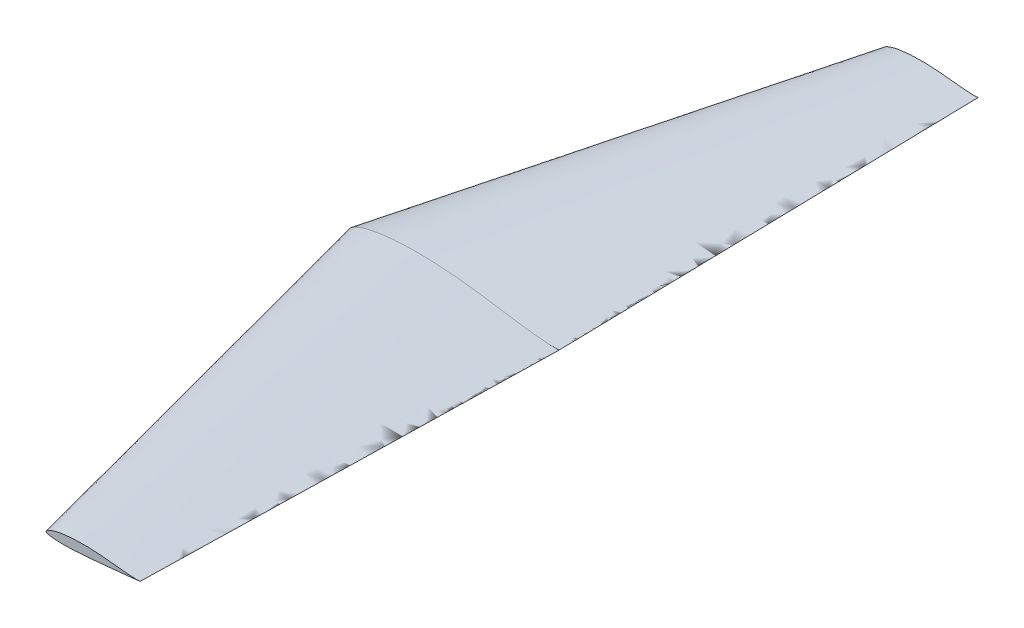
SolidWorks part; units mm, degrees
ref_plane "Front Plane" through (0, 0, 0) normal (0, 0, 1) x (1, 0, 0)
ref_plane "Top Plane" through (0, 0, 0) normal (0, 1, 0) x (1, 0, 0)
ref_plane "Right Plane" through (0, 0, 0) normal (1, 0, 0) x (0, 0, -1)
curve "Curve1"
  spline degree 3 poles (89.4117, -0.0768, 0) (90.1581, 0.0163, 0) (89.3384, -0.0489, 0) (88.6634, -0.0554, 0) (86.9988, -0.0528, 0) (84.9698, 0.0523, 0) (82.3441, 0.2429, 0) (79.2951, 0.5513, 0) (75.8494, 0.9741, 0) (72.0904, 1.4967, 0) (68.0818, 2.0963, 0) (63.8898, 2.7454, 0) (59.5721, 3.4086, 0) (55.1731, 4.0377, 0) (50.7294, 4.6, 0) (46.2733, 5.0781, 0) (41.8379, 5.4578, 0) (37.4583, 5.7341, 0) (33.171, 5.903, 0) (29.014, 5.9637, 0) (25.0243, 5.916, 0) (21.2371, 5.7575, 0) (17.6835, 5.491, 0) (14.3911, 5.12, 0) (11.385, 4.6544, 0) (8.6886, 4.1134, 0) (6.3249, 3.5134, 0) (4.3152, 2.87, 0) (2.6751, 2.2019, 0) (1.4179, 1.5316, 0) (0.6259, 0.9504, 0) (0.2409, 0.5277, 0) (0.0946, 0.3023, 0) (0.0289, 0.1579, 0) (-0.0008, 0.0428, 0) (-0.0021, -0.0493, 0) (0.0369, -0.1348, 0) (0.1141, -0.2351, 0) (0.2404, -0.3544, 0) (0.4668, -0.5223, 0) (1.0037, -0.8427, 0) (2.0204, -1.2501, 0) (3.5765, -1.7042, 0) (5.5485, -2.1302, 0) (7.9154, -2.5093, 0) (10.6594, -2.8252, 0) (13.7595, -3.0666, 0) (17.1926, -3.2314, 0) (20.9311, -3.3172, 0) (24.9437, -3.3283, 0) (29.1943, -3.2696, 0) (33.6423, -3.153, 0) (38.2418, -2.9882, 0) (42.9422, -2.7897, 0) (47.6888, -2.5669, 0) (52.4251, -2.3307, 0) (57.0933, -2.0873, 0) (61.6364, -1.844, 0) (65.999, -1.6043, 0) (70.1278, -1.373, 0) (73.9729, -1.1522, 0) (77.4858, -0.9472, 0) (80.6263, -0.7576, 0) (83.3439, -0.5873, 0) (85.6375, -0.4302, 0) (87.3906, -0.2992, 0) (88.8126, -0.1608, 0) (89.4117, -0.0768, 0) (90.1581, 0.0163, 0) (89.3384, -0.0489, 0) knots -0.013312 -0.00609 -0.00158 0 0.001669 0.006747 0.015187 0.026742 0.041155 0.058129 0.077283 0.098227 0.12058 0.143966 0.168018 0.192451 0.217075 0.24171 0.266182 0.29031 0.313903 0.336767 0.358704 0.37954 0.399122 0.417322 0.434037 0.449154 0.462553 0.474139 0.483848 0.491647 0.497539 0.499898 0.501005 0.501951 0.502492 0.502956 0.503431 0.504004 0.505035 0.506276 0.508636 0.515301 0.524213 0.535296 0.548467 0.563638 0.580726 0.599619 0.62018 0.642246 0.665633 0.690118 0.715452 0.741354 0.76752 0.793634 0.819375 0.844429 0.868488 0.891259 0.912467 0.93185 0.949165 0.964196 0.976755 0.986688 0.99391 0.99842 1 1.001669 1.006747 1.015187 periodic
sketch "CentralProfile" plane through (0, 0, 0) normal (0, 0, 1) x (1, 0, 0)
  line L0 (90, 0) -> (-10, 0) construction
  spline S1 degree 3 poles (89.3464, -0.0853) (90.1757, 0.0181) (89.2649, -0.0544) (88.5149, -0.0616) (86.6653, -0.0586) (84.411, 0.0582) (81.4935, 0.27) (78.1057, 0.6128) (74.2772, 1.0827) (70.1005, 1.6634) (65.6465, 2.3298) (60.9889, 3.051) (56.1914, 3.7881) (51.3037, 4.4871) (46.3662, 5.112) (41.4151, 5.6433) (36.4869, 6.0653) (31.6207, 6.3724) (26.8571, 6.5601) (22.2382, 6.6277) (17.8052, 6.5747) (13.5972, 6.3988) (9.6488, 6.1027) (5.9906, 5.6906) (2.6505, 5.1733) (-0.3455, 4.5723) (-2.9718, 3.9057) (-5.2048, 3.1908) (-7.0272, 2.4486) (-8.4241, 1.7038) (-9.3042, 1.0581) (-9.7319, 0.5884) (-9.8945, 0.3379) (-9.9674, 0.1775) (-10.0005, 0.0496) (-10.0019, -0.0527) (-9.9586, -0.1477) (-9.8728, -0.2592) (-9.7325, -0.3918) (-9.481, -0.5783) (-8.8844, -0.9344) (-7.7548, -1.387) (-6.0258, -1.8916) (-3.8347, -2.365) (-1.2048, -2.7863) (1.844, -3.1373) (5.2887, -3.4056) (9.1032, -3.5888) (13.2571, -3.6842) (17.7154, -3.6966) (22.4383, -3.6314) (27.3806, -3.5021) (32.4911, -3.319) (37.7137, -3.0986) (42.9877, -2.8511) (48.2502, -2.5888) (53.4371, -2.3185) (58.485, -2.0483) (63.3323, -1.782) (67.9199, -1.5251) (72.1922, -1.2798) (76.0954, -1.0522) (79.5848, -0.8416) (82.6044, -0.6524) (85.1527, -0.4778) (87.1006, -0.3324) (88.6806, -0.1786) (89.3464, -0.0853) (90.1757, 0.0181) (89.2649, -0.0544) knots -0.013312 -0.00609 -0.00158 0 0.001669 0.006747 0.015187 0.026742 0.041155 0.058129 0.077283 0.098227 0.12058 0.143966 0.168018 0.192451 0.217075 0.24171 0.266182 0.29031 0.313903 0.336767 0.358704 0.37954 0.399122 0.417322 0.434037 0.449154 0.462553 0.474139 0.483848 0.491647 0.497539 0.499898 0.501005 0.501951 0.502492 0.502956 0.503431 0.504004 0.505035 0.506276 0.508636 0.515301 0.524213 0.535296 0.548467 0.563638 0.580726 0.599619 0.62018 0.642246 0.665633 0.690118 0.715452 0.741354 0.76752 0.793634 0.819375 0.844429 0.868488 0.891259 0.912467 0.93185 0.949165 0.964196 0.976755 0.986688 0.99391 0.99842 1 1.001669 1.006747 1.015187 only from (90, 0) to (90, 0)
  dimension "D1" = 100
ref_plane "CentralProfilePlane" through (0, 0, 0) normal (0, 0, 1) x (1, 0, 0)
curve "Curve2"
  spline degree 3 poles (49.6732, -0.0427, 200) (50.0878, 0.0091, 200) (49.6325, -0.0272, 200) (49.2574, -0.0308, 200) (48.3327, -0.0294, 200) (47.2055, 0.0291, 200) (45.7467, 0.1349, 200) (44.0528, 0.3063, 200) (42.1386, 0.5412, 200) (40.0502, 0.8315, 200) (37.8232, 1.1646, 200) (35.4944, 1.5252, 200) (33.0956, 1.8937, 200) (30.6517, 2.2432, 200) (28.183, 2.5556, 200) (25.7074, 2.8212, 200) (23.2433, 3.0321, 200) (20.8102, 3.1856, 200) (18.4283, 3.2794, 200) (16.1189, 3.3132, 200) (13.9024, 3.2866, 200) (11.7984, 3.1986, 200) (9.8242, 3.0505, 200) (7.9951, 2.8444, 200) (6.325, 2.5858, 200) (4.827, 2.2852, 200) (3.5139, 1.9519, 200) (2.3974, 1.5945, 200) (1.4862, 1.2233, 200) (0.7877, 0.8509, 200) (0.3477, 0.528, 200) (0.1338, 0.2932, 200) (0.0525, 0.1679, 200) (0.0161, 0.0877, 200) (-0.0005, 0.0238, 200) (-0.0012, -0.0274, 200) (0.0205, -0.0749, 200) (0.0634, -0.1306, 200) (0.1336, -0.1969, 200) (0.2593, -0.2902, 200) (0.5576, -0.4682, 200) (1.1224, -0.6945, 200) (1.9869, -0.9468, 200) (3.0825, -1.1835, 200) (4.3974, -1.3941, 200) (5.9219, -1.5695, 200) (7.6442, -1.7037, 200) (9.5515, -1.7952, 200) (11.6284, -1.8429, 200) (13.8576, -1.849, 200) (16.2191, -1.8164, 200) (18.6902, -1.7517, 200) (21.2455, -1.6601, 200) (23.8568, -1.5499, 200) (26.4938, -1.4261, 200) (29.125, -1.2948, 200) (31.7185, -1.1596, 200) (34.2425, -1.0245, 200) (36.6661, -0.8913, 200) (38.9599, -0.7628, 200) (41.0961, -0.6401, 200) (43.0477, -0.5262, 200) (44.7924, -0.4209, 200) (46.3022, -0.3263, 200) (47.5764, -0.239, 200) (48.5503, -0.1662, 200) (49.3403, -0.0893, 200) (49.6732, -0.0427, 200) (50.0878, 0.0091, 200) (49.6325, -0.0272, 200) knots -0.013312 -0.00609 -0.00158 0 0.001669 0.006747 0.015187 0.026742 0.041155 0.058129 0.077283 0.098227 0.12058 0.143966 0.168018 0.192451 0.217075 0.24171 0.266182 0.29031 0.313903 0.336767 0.358704 0.37954 0.399122 0.417322 0.434037 0.449154 0.462553 0.474139 0.483848 0.491647 0.497539 0.499898 0.501005 0.501951 0.502492 0.502956 0.503431 0.504004 0.505035 0.506276 0.508636 0.515301 0.524213 0.535296 0.548467 0.563638 0.580726 0.599619 0.62018 0.642246 0.665633 0.690118 0.715452 0.741354 0.76752 0.793634 0.819375 0.844429 0.868488 0.891259 0.912467 0.93185 0.949165 0.964196 0.976755 0.986688 0.99391 0.99842 1 1.001669 1.006747 1.015187 periodic
ref_plane "OutsideProfilePlane" through (0, 0, 200) normal (0, 0, 1) x (1, 0, 0)
sketch "OutsideProfile" plane through (0, 0, 200) normal (0, 0, 1) x (1, 0, 0)
  line L0 (90, 4.4083) -> (45.0389, 2.538) construction
  spline S1 degree 3 poles (89.7077, 4.3575) (90.0786, 4.4198) (89.6705, 4.3699) (89.3334, 4.3523) (88.5017, 4.3183) (87.4858, 4.3279) (86.17, 4.3674) (84.6402, 4.4569) (82.9098, 4.5951) (81.0207, 4.7766) (79.0053, 4.9912) (76.8973, 5.2267) (74.7261, 5.4665) (72.5151, 5.6876) (70.2831, 5.8744) (68.0467, 6.0188) (65.8227, 6.1145) (63.6288, 6.1597) (61.4834, 6.1533) (59.4052, 6.0955) (57.413, 5.9871) (55.5243, 5.8277) (53.7546, 5.6193) (52.1176, 5.3641) (50.6256, 5.0679) (49.29, 4.7405) (48.1218, 4.3906) (47.1314, 4.0266) (46.3261, 3.6581) (45.7123, 3.2965) (45.3289, 2.9894) (45.1455, 2.77) (45.0772, 2.6543) (45.0474, 2.5808) (45.035, 2.5227) (45.0363, 2.4766) (45.0576, 2.4347) (45.0983, 2.3862) (45.1639, 2.3293) (45.2806, 2.2502) (45.5556, 2.1015) (46.0722, 1.9196) (46.8592, 1.7257) (47.8535, 1.5546) (49.044, 1.4154) (50.4216, 1.3157) (51.9755, 1.2608) (53.6942, 1.2512) (55.5637, 1.2875) (57.5686, 1.367) (59.691, 1.4864) (61.9107, 1.6389) (64.2051, 1.8187) (66.5492, 2.0175) (68.9159, 2.2294) (71.2771, 2.4477) (73.6041, 2.6683) (75.8687, 2.886) (78.0432, 3.0983) (80.101, 3.3013) (82.0173, 3.4931) (83.768, 3.6699) (85.333, 3.8312) (86.6871, 3.9739) (87.8296, 4.101) (88.7027, 4.2035) (89.4102, 4.3028) (89.7077, 4.3575) (90.0786, 4.4198) (89.6705, 4.3699) knots -0.013312 -0.00609 -0.00158 0 0.001669 0.006747 0.015187 0.026742 0.041155 0.058129 0.077283 0.098227 0.12058 0.143966 0.168018 0.192451 0.217075 0.24171 0.266182 0.29031 0.313903 0.336767 0.358704 0.37954 0.399122 0.417322 0.434037 0.449154 0.462553 0.474139 0.483848 0.491647 0.497539 0.499898 0.501005 0.501951 0.502492 0.502956 0.503431 0.504004 0.505035 0.506276 0.508636 0.515301 0.524213 0.535296 0.548467 0.563638 0.580726 0.599619 0.62018 0.642246 0.665633 0.690118 0.715452 0.741354 0.76752 0.793634 0.819375 0.844429 0.868488 0.891259 0.912467 0.93185 0.949165 0.964196 0.976755 0.986688 0.99391 0.99842 1 1.001669 1.006747 1.015187 only from (90, 4.4083) to (90, 4.4083)
  point P1 (45.0389, 2.538)
  dimension "D1" = 45
ref_axis "Axis3" through (-10, 0, 0) along (0.2653, 0.0122, 0.9641)
loft "Loft3" add profiles "OutsideProfile", "CentralProfile" connector at (45.0454, 2.4603, 200) connector at (-9.9991, -0.023, 0)
mirror "Mirror1" about plane through (0, 0, 0) normal (0, 0, 1) of "Loft3"
